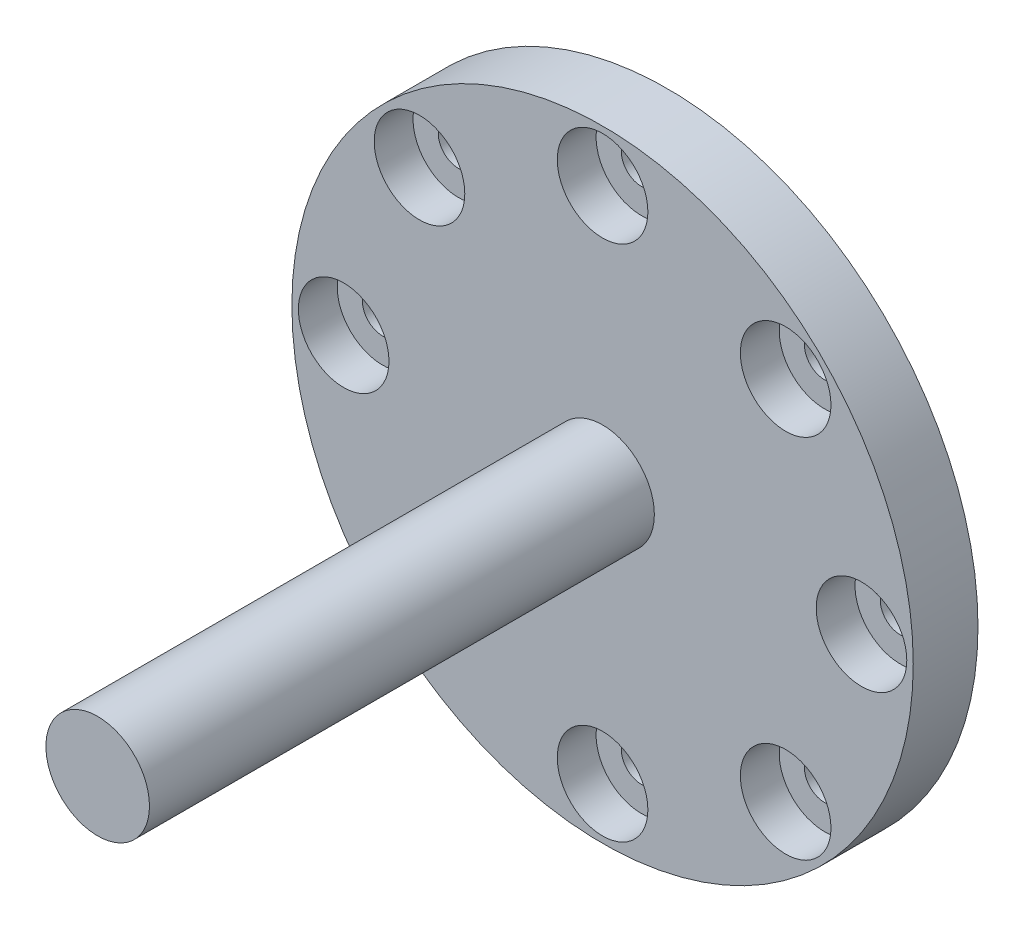
SolidWorks part; units mm, degrees
ref_plane "Front Plane" through (0, 0, 0) normal (0, 0, 1) x (1, 0, 0)
ref_plane "Top Plane" through (0, 0, 0) normal (0, 1, 0) x (1, 0, 0)
ref_plane "Right Plane" through (0, 0, 0) normal (1, 0, 0) x (0, 0, -1)
ref_axis "Axis1" through (0, 0, 5.5) along (0, 0, -1)
sketch "Sketch6" plane through (0, 0, 0) normal (0, 0, 1) x (1, 0, 0)
  circle A0 centre (0, 0) radius 24
extrude "Boss-Extrude1" add sketch "Sketch6" along normal blind 5
sketch "Sketch8" plane through (0, 0, 0) normal (0, 0, -1) x (-1, 0, 0)
  line L0 (0, 20) -> (0, 0) construction
  circle A0 centre (0, 20) radius 1.55
  circle A1 centre (14.1421, 14.1421) radius 1.55
  circle A2 centre (20, 0) radius 1.55
  circle A3 centre (14.1421, -14.1421) radius 1.55
  circle A4 centre (0, -20) radius 1.55
  circle A5 centre (-14.1421, -14.1421) radius 1.55
  circle A6 centre (-20, 0) radius 1.55
  circle A7 centre (-14.1421, 14.1421) radius 1.55
  dimension "D1" = 8
extrude "Cut-Extrude6" cut sketch "Sketch8" against normal up to surface (5 mm away) up to face at (24, 0, 5)
sketch "Sketch10" plane through (0, 0, 5) normal (0, 0, 1) x (1, 0, 0)
  circle A0 centre (0, 0) radius 4
extrude "Boss-Extrude2" add sketch "Sketch10" along normal blind 39
sketch "Sketch11" plane through (0, 0, 5) normal (0, 0, 1) x (1, 0, 0)
  circle A0 centre (0, 20) radius 3.5
  circle A1 centre (14.1421, 14.1421) radius 3.5
  circle A2 centre (20, 0) radius 3.5
  circle A3 centre (14.1421, -14.1421) radius 3.5
  circle A4 centre (0, -20) radius 3.5
  circle A5 centre (-14.1421, -14.1421) radius 3.5
  circle A6 centre (-20, 0) radius 3.5
  circle A7 centre (-14.1421, 14.1421) radius 3.5
  point P19 (0, 0)
  dimension "D1" = 8
extrude "Cut-Extrude8" cut sketch "Sketch11" against normal blind 3
